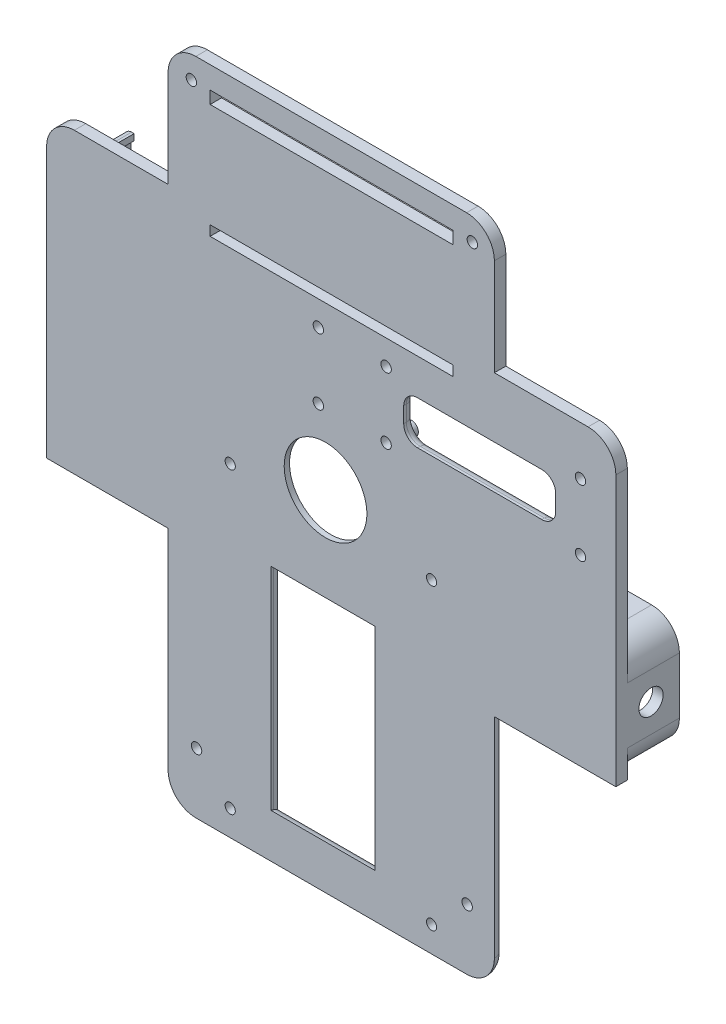
SolidWorks part; units mm, degrees
ref_plane "Front Plane" through (0, 0, 0) normal (0, 0, 1) x (1, 0, 0)
ref_plane "Top Plane" through (0, 0, 0) normal (0, 1, 0) x (1, 0, 0)
ref_plane "Right Plane" through (0, 0, 0) normal (1, 0, 0) x (0, 0, -1)
sketch "Sketch1" plane through (0, 0, 0) normal (0, 0, 1) x (1, 0, 0)
  line L1 (38.8192, -100.5011) -> (-39.1808, -100.5011)
  line L2 (46.8192, -92.5011) -> (46.8192, 81.4989)
  line L3 (38.8192, 89.4989) -> (-39.1808, 89.4989)
  line L4 (-47.1808, -92.5011) -> (-47.1808, 81.4989)
  circle A0 centre (-40.48, 82.9746) radius 1.5
  circle A1 centre (-38.98, -83.0066) radius 1.5
  circle A2 centre (38.98, -83.0066) radius 1.5
  circle A3 centre (40.48, 82.9746) radius 1.5
  arc A4 (-39.1808, 89.4989) -> (-47.1808, 81.4989) centre (-39.1808, 81.4989) ccw
  arc A5 (-47.1808, -92.5011) -> (-39.1808, -100.5011) centre (-39.1808, -92.5011) ccw
  arc A6 (38.8192, -100.5011) -> (46.8192, -92.5011) centre (38.8192, -92.5011) ccw
  arc A7 (46.8192, 81.4989) -> (38.8192, 89.4989) centre (38.8192, 81.4989) ccw
  point P0 (0, 0)
  point P6 (0, 0)
  point P9 (-47.1808, 89.4989)
  point P12 (-47.1808, -100.5011)
  point P25 (46.8192, 89.4989)
  dimension "D5" = 3
  dimension "D6" = 3
  dimension "D7" = 8
  dimension "D8" = 8
  dimension "D1" = 94
  dimension "D2" = 190
  dimension "D3" = 80.9601
  dimension "D4" = 77.9601
extrude "Boss-Extrude2" add sketch "Sketch1" along normal blind 3.302 contours L2 A7 L3 A4 L4 A5 L1 A6 | A3 | A0 | A2 | A1
sketch "Sketch51" plane through (0, 0, 0) normal (0, 0, -1) x (-1, 0, 0)
  line L0 (47.1808, -92.5011) -> (47.1808, 81.4989) construction
  line L1 (47.1808, 53.5672) -> (74.1808, 53.5672)
  line L2 (47.1808, 53.5672) -> (47.1808, -32.2346)
  line L3 (47.1808, -32.2346) -> (82.1808, -32.2346)
  line L4 (82.1808, 45.5672) -> (82.1808, -32.2346)
  line L5 (-46.8192, -92.5011) -> (-46.8192, 81.4989) construction
  line L6 (-46.8192, 53.5672) -> (-73.8192, 53.5672)
  line L7 (-46.8192, 53.5672) -> (-46.8192, -32.2346)
  line L8 (-46.8192, -32.2346) -> (-81.8192, -32.2346)
  line L9 (-81.8192, 45.5672) -> (-81.8192, -32.2346)
  arc A0 (82.1808, 45.5672) -> (74.1808, 53.5672) centre (74.1808, 45.5672) ccw
  arc A1 (-73.8192, 53.5672) -> (-81.8192, 45.5672) centre (-73.8192, 45.5672) ccw
  point P14 (82.1808, 53.5672)
  point P17 (-81.8192, 53.5672)
  dimension "D3" = 8
  dimension "D1" = 35
  dimension "D2" = 35
extrude "Boss-Extrude20" add sketch "Sketch51" against normal blind 3.302 contours L2 L3 L4 A0 L1 | L7 L8 L9 A1 L6
sketch "Sketch5" plane through (0, 0, 0) normal (0, 0, -1) x (-1, 0, 0)
  circle A0 centre (-28.7185, -7.157) radius 2.5
  circle A1 centre (-28.7185, -93.136) radius 2.5
  circle A2 centre (29.2815, -93.136) radius 2.5
  circle A3 centre (29.2815, -7.157) radius 2.5
  dimension "D3" = 5
  dimension "D4" = 5
  dimension "D1" = 58
  dimension "D2" = 85.979
  dimension "D5" = 85.979
extrude "jetson-mount" add sketch "Sketch5" along normal blind 5
hole_wizard "CSK for M3 Flat Head Machine Screw1" positions "Sketch18" profile "Sketch19" countersink size "M3" standard "ANSI Metric" end condition through all
sketch "Sketch18" plane through (0, 0, -5) normal (0, 0, -1) x (-1, 0, 0)
  point P0 (-28.7185, -7.157)
  point P3 (29.2815, -7.157)
  point P6 (-28.7185, -93.136)
  point P9 (29.2815, -93.136)
sketch "Sketch19" plane through (28.7185, -7.157, -5) normal (1, 0, 0) x (0, 1, 0)
  line L0 (0, 0) -> (0, 8.302)
  line L1 (0, 8.302) -> (1.465, 8.302)
  line L2 (1.465, 8.302) -> (1.465, 1.685)
  line L3 (1.465, 1.685) -> (3.15, 0)
  line L5 (3.15, 0) -> (0, 0)
  line L6 (-1.465, 1.685) -> (-3.15, 0) construction
  line L11 (0, -6.35) -> (0, 107.95) construction
  dimension "Thru Hole Dia." = 2.93
  dimension "Thru Hole Depth" = 8.302
  dimension "Near C'Sink Dia." = 6.3
  dimension "Near C'Sink Angle" = 90
sketch "Sketch20" plane through (0, 0, 0) normal (0, 0, -1) x (-1, 0, 0)
  line L1 (-12.4815, -26.8879) -> (17.5185, -26.8879)
  line L2 (-12.4815, -26.8879) -> (-12.4815, -87.8101)
  line L3 (-12.4815, -87.8101) -> (17.5185, -87.8101)
  line L4 (17.5185, -26.8879) -> (17.5185, -87.8101)
  dimension "D1" = 30
extrude "Cut-Extrude3" cut sketch "Sketch20" against normal through all contours L2 L1 L4 L3
sketch "Sketch49" plane through (0, 0, 0) normal (0, 0, -1) x (-1, 0, 0)
  circle A0 centre (1.8271, 0) radius 11.9099
extrude "wire-hole" cut sketch "Sketch49" against normal through all contours A0
sketch "Sketch41" plane through (0, 0, 0) normal (0, 0, -1) x (-1, 0, 0)
  circle A0 centre (-71.6281, 39.5046) radius 2
  circle A1 centre (-71.6281, 20.5046) radius 2
  circle A2 centre (-15.6281, 20.5046) radius 2
  circle A3 centre (-15.6281, 39.5046) radius 2
  dimension "D3" = 4
  dimension "D4" = 4
  dimension "D1" = 19
  dimension "D2" = 56
extrude "multiplxr-mount" add sketch "Sketch41" along normal blind 4
sketch "Sketch33" plane through (0, 0, 0) normal (0, 0, -1) x (-1, 0, 0)
  circle A0 centre (3.8941, 39.5186) radius 2
  circle A1 centre (3.8941, 20.5186) radius 2
  dimension "D2" = 4
  dimension "D3" = 4
  dimension "D1" = 19
extrude "rc-multipl" add sketch "Sketch33" along normal blind 4
hole_wizard "Ø3.0mm Dowel Hole2" positions "Sketch39" profile "Sketch40" hole size "Ø3.0" standard "ANSI Metric" end condition through all
sketch "Sketch39" plane through (0, 0, -4) normal (0, 0, -1) x (-1, 0, 0)
  point P0 (3.8941, 39.5186)
  point P3 (3.8941, 20.5186)
sketch "Sketch40" plane through (-3.8941, 39.5186, -4) normal (1, 0, 0) x (0, 1, 0)
  line L0 (0, 0) -> (0, 7.302)
  line L1 (0, 7.302) -> (1.5, 7.302)
  line L2 (1.5, 7.302) -> (1.5, 0)
  line L5 (1.5, 0) -> (0, 0)
  line L11 (0, -6.35) -> (0, 107.95) construction
  dimension "Thru Hole Dia." = 3
  dimension "Thru Hole Depth" = 7.302
hole_wizard "Ø3.0mm Dowel Hole3" positions "Sketch42" profile "Sketch43" hole size "Ø3.0" standard "ANSI Metric" end condition through all
sketch "Sketch42" plane through (0, 0, -4) normal (0, 0, -1) x (-1, 0, 0)
  point P0 (-71.6281, 39.5046)
  point P3 (-71.6281, 20.5046)
  point P6 (-15.6281, 20.5046)
  point P9 (-15.6281, 39.5046)
sketch "Sketch43" plane through (71.6281, 39.5046, -4) normal (1, 0, 0) x (0, 1, 0)
  line L0 (0, 0) -> (0, 7.302)
  line L1 (0, 7.302) -> (1.5, 7.302)
  line L2 (1.5, 7.302) -> (1.5, 0)
  line L5 (1.5, 0) -> (0, 0)
  line L11 (0, -6.35) -> (0, 107.95) construction
  dimension "Thru Hole Dia." = 3
  dimension "Thru Hole Depth" = 7.302
fillet "Fillet1" radius 3.4976 1 edges at (-2.5185, -26.8879, 0)
fillet "Fillet3" radius 3.8024 1 edges at (-2.5185, -87.8101, 0)
fillet "Fillet4" radius 3.2436 5 edges at (-0.1808, -100.5011, 0) (46.8192, -62.3679, 0) (44.4761, -98.158, 0) (-47.1808, -62.3679, 0) (-44.8376, -98.158, 0)
chamfer "Chamfer1" distance 4.699 angle 20.608 1 edges at (-13.737, 0, 0) first distance on face at (-1.8941, 20.5186, 0)
sketch "Sketch50" plane through (0, 0, 0) normal (0, 0, -1) x (-1, 0, 0)
  circle A0 centre (21.9336, 29.6343) radius 3.1628
extrude "rc-mult-sprt" add sketch "Sketch50" along normal blind 3.048
sketch "Sketch53" plane through (0, 0, 0) normal (0, 0, -1) x (-1, 0, 0)
  line L0 (-73.8192, 0) -> (-66.8192, 0)
  line L1 (-81.8192, 45.5672) -> (-81.8192, -32.2346) construction
  line L2 (-66.8192, 0) -> (-73.7876, -2.7844)
  line L3 (-78.8192, -10.2133) -> (-78.8192, -22.0032)
  line L4 (-73.8042, -29.4255) -> (-66.8192, -32.2346)
  line L5 (-43.5756, -32.2346) -> (-81.8192, -32.2346) construction
  line L6 (-66.8192, -32.2346) -> (-73.8192, -32.2346)
  line L7 (-81.8192, -24.2346) -> (-81.8192, -8)
  line L16 (0.1808, 53.5672) -> (0.1808, -100.5011)
  line L17 (39.1808, -100.5011) -> (-38.8192, -100.5011) construction
  line L18 (67.1808, -32.2346) -> (74.1808, -32.2346)
  line L19 (74.1658, -29.4255) -> (67.1808, -32.2346)
  line L20 (79.1808, -10.2133) -> (79.1808, -22.0032)
  line L21 (67.1808, 0) -> (74.1492, -2.7844)
  line L22 (74.1808, 0) -> (67.1808, 0)
  line L23 (82.1808, -24.2346) -> (82.1808, -8)
  arc A0 (82.1808, -24.2346) -> (74.1808, -32.2346) centre (74.1808, -24.2346) cw
  arc A1 (82.1808, -8) -> (74.1808, 0) centre (74.1808, -8) ccw
  arc A2 (79.1808, -10.2133) -> (74.1492, -2.7844) centre (71.1808, -10.2133) ccw
  arc A3 (79.1808, -22.0032) -> (74.1658, -29.4255) centre (71.1808, -22.0032) cw
  arc A4 (-81.8192, -24.2346) -> (-73.8192, -32.2346) centre (-73.8192, -24.2346) ccw
  arc A5 (-78.8192, -22.0032) -> (-73.8042, -29.4255) centre (-70.8192, -22.0032) ccw
  arc A6 (-73.7876, -2.7844) -> (-78.8192, -10.2133) centre (-70.8192, -10.2133) ccw
  arc A7 (-73.8192, 0) -> (-81.8192, -8) centre (-73.8192, -8) ccw
  point P26 (82.1808, -32.2346)
  point P29 (82.1808, 0)
  point P32 (79.1808, -4.7949)
  point P35 (79.1808, -27.4086)
  point P38 (-81.8192, -32.2346)
  point P41 (-78.8192, -27.4086)
  point P44 (-78.8192, -4.7949)
  point P47 (-81.8192, 0)
  dimension "D6" = 8
  dimension "D1" = 4.7949
  dimension "D2" = 4.826
  dimension "D3" = 3
  dimension "D4" = 15
  dimension "D5" = 15
extrude "ant-mount" add sketch "Sketch53" along normal blind 15 contours L7 A7 L0 L2 A6 L3 A5 L4 L6 A4 | L18 A0 L23 A1 L22 L21 A2 L20 A3 L19
sketch "Sketch54" plane through (81.8192, 0, 0) normal (1, 0, 0) x (0, 0, -1)
  circle A0 centre (6.8256, -16.1173) radius 3.5
  dimension "D1" = 7
extrude "ant1-hole" cut sketch "Sketch54" against normal blind 15
sketch "Sketch55" plane through (-82.1808, 0, 0) normal (-1, 0, 0) x (0, 0, 1)
  circle A0 centre (-6.8256, -16.1173) radius 3.5
  dimension "D1" = 7
extrude "ant2-hole" cut sketch "Sketch55" against normal blind 15
sketch "Sketch56" plane through (0, 0, 0) normal (0, 0, -1) x (-1, 0, 0)
  line L1 (54.1945, 43.2396) -> (74.1945, 43.2396)
  line L2 (54.1945, 43.2396) -> (54.1945, 6.2396)
  line L3 (54.1945, 6.2396) -> (74.1945, 6.2396)
  line L4 (74.1945, 43.2396) -> (74.1945, 6.2396)
  line L6 (52.3945, 43.0396) -> (52.3945, 6.4396)
  line L7 (54.3945, 4.4396) -> (73.9945, 4.4396)
  line L8 (75.9945, 6.4396) -> (75.9945, 43.0396)
  line L9 (73.9945, 45.0396) -> (54.3945, 45.0396)
  arc A0 (75.9945, 6.4396) -> (73.9945, 4.4396) centre (73.9945, 6.4396) cw
  arc A1 (73.9945, 45.0396) -> (75.9945, 43.0396) centre (73.9945, 43.0396) cw
  arc A2 (52.3945, 43.0396) -> (54.3945, 45.0396) centre (54.3945, 43.0396) cw
  arc A3 (52.3945, 6.4396) -> (54.3945, 4.4396) centre (54.3945, 6.4396) ccw
  dimension "D7" = 2
  dimension "D1" = 20
  dimension "D2" = 37
  dimension "D3" = 1.8
  dimension "D4" = 1.8
  dimension "D5" = 1.8
  dimension "D6" = 1.8
extrude "rx-holder" add sketch "Sketch56" along normal blind 13 contours L4 L1 L2 L3 | L6 A3 L7 A0 L8 A1 L9 A2 region at (-64.1945, 24.7396, 0)
sketch "Sketch57" plane through (0, 45.0396, 0) normal (0, 1, 0) x (1, 0, 0)
  line L0 (-73.9945, 13) -> (-54.3945, 13) construction
  line L1 (-73.2704, 13) -> (-54.8945, 13)
  line L2 (-73.2704, 13) -> (-73.2704, 7.1666)
  line L3 (-73.2704, 7.1666) -> (-54.8945, 7.1666)
  line L4 (-54.8945, 13) -> (-54.8945, 7.1666)
extrude "rx-ant-cutout" cut sketch "Sketch57" against normal blind 13 contours L2 L1 L4 L3
sketch "Sketch58" plane through (0, 0, 0) normal (0, 0, -1) x (-1, 0, 0)
sketch "Sketch59" plane through (0, 0, 0) normal (0, 0, -1) x (-1, 0, 0)
  line L1 (-34.926, 83.1512) -> (35.074, 83.1512)
  line L2 (-34.926, 83.1512) -> (-34.926, 79.5512)
  line L3 (-34.926, 79.5512) -> (35.074, 79.5512)
  line L4 (35.074, 83.1512) -> (35.074, 79.5512)
  line L5 (-34.926, 49.5512) -> (35.074, 49.5512)
  line L6 (-34.926, 49.5512) -> (-34.926, 46.6591)
  line L7 (-34.926, 46.6591) -> (35.074, 46.6591)
  line L8 (35.074, 49.5512) -> (35.074, 46.6591)
  dimension "D1" = 70
  dimension "D2" = 3.6
  dimension "D3" = 30
extrude "Cut-Extrude8" cut sketch "Sketch59" against normal blind 13 contours L8 L5 L6 L7 | L2 L1 L4 L3 region at (-0.074, 48.1051, 0)
sketch "Sketch60" plane through (0, 0, 0) normal (0, 0, -1) x (-1, 0, 0)
  line L1 (-60.4888, 36.254) -> (-24.6968, 36.254)
  line L2 (-64.4888, 32.254) -> (-64.4888, 27.7784)
  line L3 (-60.4888, 23.7784) -> (-24.6968, 23.7784)
  line L4 (-20.6968, 32.254) -> (-20.6968, 27.7784)
  arc A0 (-20.6968, 32.254) -> (-24.6968, 36.254) centre (-24.6968, 32.254) ccw
  arc A1 (-24.6968, 23.7784) -> (-20.6968, 27.7784) centre (-24.6968, 27.7784) ccw
  arc A2 (-64.4888, 27.7784) -> (-60.4888, 23.7784) centre (-60.4888, 27.7784) ccw
  arc A3 (-64.4888, 32.254) -> (-60.4888, 36.254) centre (-60.4888, 32.254) cw
  dimension "D1" = 4
extrude "Cut-Extrude9" cut sketch "Sketch60" against normal blind 13
fillet "Fillet5" radius 2.54 8 edges at (21.8684, 35.0825, 0) (20.6968, 30.0162, 0) (21.8684, 24.95, 0) (63.3173, 24.95, 0) (64.4888, 30.0162, 0) (63.3173, 35.0825, 0) (42.5928, 23.7784, 0) (42.5928, 36.254, 0)
fillet "Fillet6" radius 2.54 2 edges at (-17.5185, -57.4876, 0) (12.4815, -57.4876, 0)
